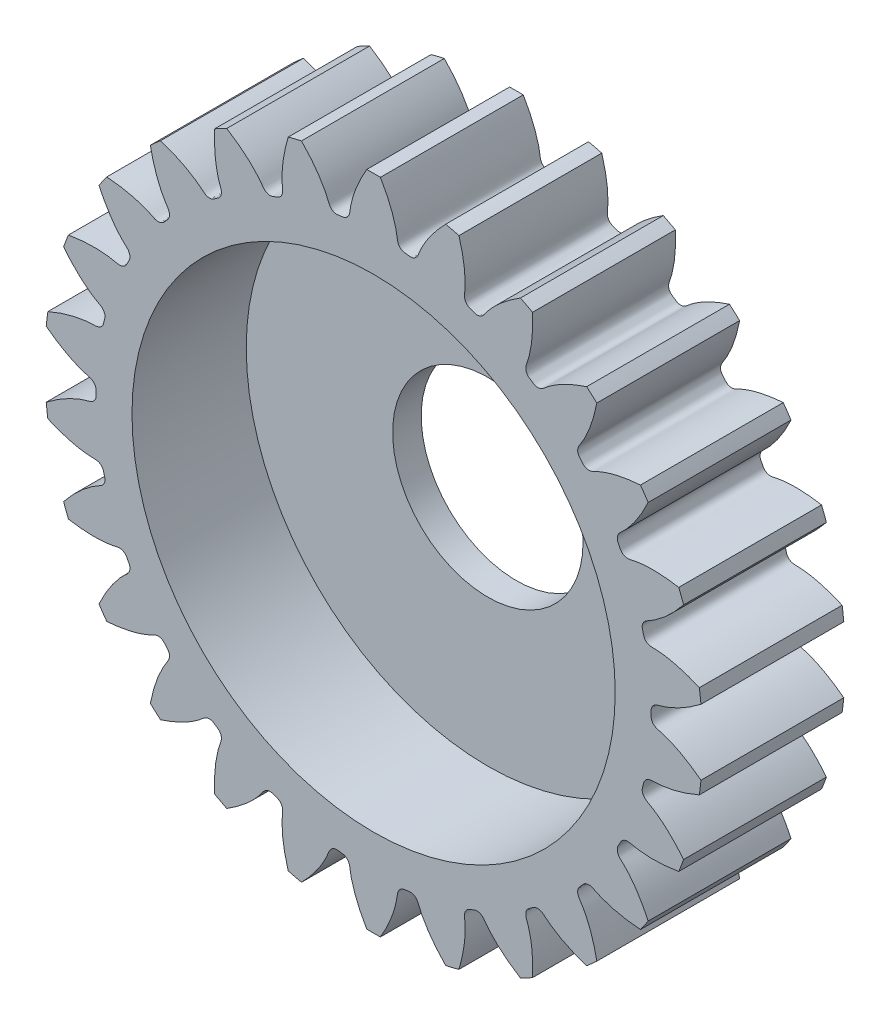
SolidWorks part; units mm, degrees
material "Д16 ГОСТ 4784-97"
ref_plane "FRONT" through (0, 0, 0) normal (0, 0, 1) x (1, 0, 0)
ref_plane "TOP" through (0, 0, 0) normal (0, 1, 0) x (1, 0, 0)
ref_plane "RIGHT" through (0, 0, 0) normal (1, 0, 0) x (0, 0, -1)
ref_axis "Ось1" through (0, 0, 50) along (0, 0, -1)
sketch "SketchRevolveSpurAssemblyNew2Pinion" plane through (0, 0, 0) normal (1, 0, 0) x (0, 0, -1)
  line L0 (0, 0) -> (1, 0) construction
  line L1 (-4, 0) -> (-4, 13.8221)
  line L2 (-4, 13.8221) -> (2, 13.8221)
  line L3 (2, 13.8221) -> (2, 0)
  line L4 (2, 0) -> (-4, 0)
  dimension "D1" = 4
  dimension "D2" = 6
revolve "SpurAssemblyNew2Pinion" add sketch "SketchRevolveSpurAssemblyNew2Pinion" angle 360 about L0
sketch "SketchToothSpurAssemblyNew2Pinion" plane through (0, 0, 0) normal (0, 0, 1) x (1, 0, 0)
  arc A0 (13.8145, 1.4289) -> (13.8145, -1.4289) centre (0, 0) cw
  spline S0 degree 3 poles (13.8145, -1.4289) (13.7267, -1.3599) (13.5952, -1.2613) (13.4189, -1.1388) (13.2926, -1.0553) (13.1699, -0.9783) (13.051, -0.9075) (12.9361, -0.8427) (12.8254, -0.7837) (12.7191, -0.7302) (12.6175, -0.6819) (12.5207, -0.6387) (12.4289, -0.6003) (12.3422, -0.5664) (12.2609, -0.5368) (12.185, -0.5112) (12.1147, -0.4893) (12.0271, -0.4637) (11.9541, -0.4482) (11.8978, -0.428) (11.8759, -0.419) (11.8534, -0.4085) (11.8302, -0.3959) (11.806, -0.3807) (11.7805, -0.3619) (11.7539, -0.3382) (11.7266, -0.3079) (11.7001, -0.2694) (11.6771, -0.2215) (11.6616, -0.1665) (11.6562, -0.0913) (11.6603, 0) (11.6562, 0.0913) (11.6616, 0.1665) (11.6771, 0.2215) (11.7001, 0.2694) (11.7266, 0.3079) (11.7539, 0.3382) (11.7805, 0.3619) (11.806, 0.3807) (11.8302, 0.3959) (11.8534, 0.4085) (11.8759, 0.419) (11.8978, 0.428) (11.9541, 0.4482) (12.0271, 0.4637) (12.1147, 0.4893) (12.185, 0.5112) (12.2609, 0.5368) (12.3422, 0.5664) (12.4289, 0.6003) (12.5207, 0.6387) (12.6175, 0.6819) (12.7191, 0.7302) (12.8254, 0.7837) (12.9361, 0.8427) (13.051, 0.9075) (13.1699, 0.9783) (13.2926, 1.0553) (13.4189, 1.1388) (13.5952, 1.2613) (13.7267, 1.3599) (13.8145, 1.4289) knots 0 0 0 0 0.061766 0.090857 0.118755 0.145459 0.170969 0.195285 0.218406 0.240334 0.261068 0.280608 0.298954 0.316106 0.332064 0.346827 0.360397 0.372773 0.397299 0.401522 0.405868 0.410405 0.415225 0.420444 0.426212 0.432709 0.440141 0.448702 0.45849 0.469388 0.4801 0.5 0.5199 0.530612 0.54151 0.551298 0.559859 0.567291 0.573788 0.579556 0.584775 0.589595 0.594132 0.598478 0.602701 0.627227 0.639603 0.653173 0.667936 0.683894 0.701046 0.719392 0.738932 0.759666 0.781594 0.804715 0.829031 0.854541 0.881245 0.909143 0.938234 1 1 1 1
extrude "ToothExtrudeCutSpurAssemblyNew2Pinion" cut sketch "SketchToothSpurAssemblyNew2Pinion" against normal blind 4 and the other way blind 4
pattern_circular "PatternSpurAssemblyNew2Pinion" count 26 every 13.846 about axis through (0, 0, 50) along (0, 0, -1) of "ToothExtrudeCutSpurAssemblyNew2Pinion"
sketch "AuxiliarySketchSpurAssemblyNew2Pinion" plane through (0, 0, 0) normal (0, 0, 1) x (1, 0, 0)
  circle A0 centre (0, 0) radius 12.5 construction
  circle A1 centre (0, 0) radius 11.7462 construction
  circle A2 centre (0, 0) radius 11.9829 construction
  circle A3 centre (0, 0) radius 13.8221 construction
  circle A4 centre (0, 0) radius 11.6587 construction
  dimension "PitchDiameter" = 25
  dimension "BaseDiameter" = 23.4923
  dimension "FormDiameter" = 23.9658
  dimension "MajorDiameter" = 27.6442
  dimension "MinorDiameter" = 23.3173
sketch "Эскиз3" plane through (0, 0, -2) normal (0, 0, -1) x (-1, 0, 0)
  circle A0 centre (0, 0) radius 9.5
sketch "Эскиз2" plane through (0, 0, 4) normal (0, 0, 1) x (1, 0, 0)
  circle A0 centre (0, 0) radius 10.15
extrude "Вырез-Вытянуть2" cut sketch "Эскиз2" against normal blind 4.8
sketch "Эскиз1" plane through (0, 0, -0.8) normal (0, 0, 1) x (1, 0, 0)
  circle A0 centre (0, 0) radius 7 construction
  circle A1 centre (0, 0) radius 8.25 construction
  circle A2 centre (0, 7) radius 1.25
  circle A3 centre (7, 0) radius 1.25
  circle A4 centre (0, -7) radius 1.25
  circle A5 centre (-7, 0) radius 1.25
  dimension "D1" = 14
  dimension "D2" = 16.5
sketch "Эскиз4" plane through (0, 0, -0.8) normal (0, 0, 1) x (1, 0, 0)
  circle A0 centre (0, 0) radius 4
  dimension "D1" = 8
extrude "Вырез-Вытянуть3" cut sketch "Эскиз4" against normal through all
